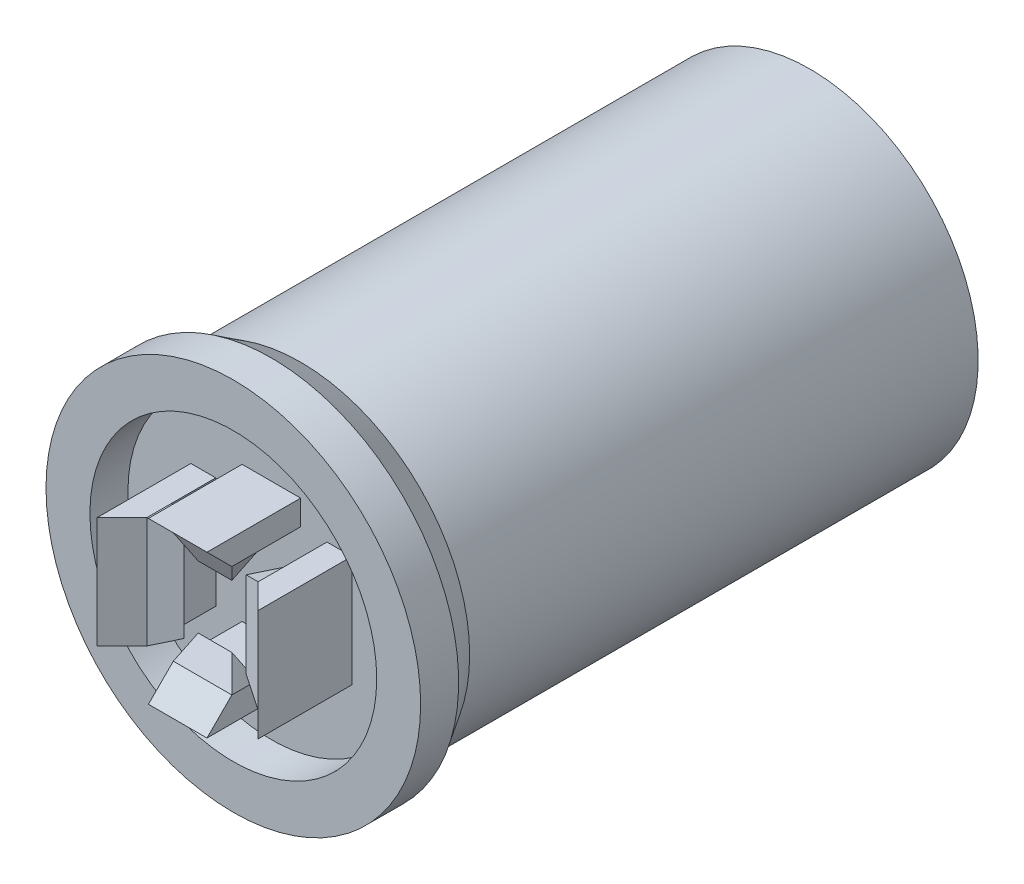
SolidWorks part; units mm, degrees
ref_plane "Front Plane" through (0, 0, 0) normal (0, 0, 1) x (1, 0, 0)
ref_plane "Top Plane" through (0, 0, 0) normal (0, 1, 0) x (1, 0, 0)
ref_plane "Right Plane" through (0, 0, 0) normal (1, 0, 0) x (0, 0, -1)
sketch "Sketch1" plane through (0, 0, 0) normal (0, 0, 1) x (1, 0, 0)
  circle A0 centre (0, 0) radius 6.4
  dimension "D1" = 12.8
extrude "Boss-Extrude1" add sketch "Sketch1" along normal blind 1.3
sketch "Sketch3" plane through (0, 0, 0) normal (0, 0, -1) x (-1, 0, 0)
  circle A0 centre (0, 0) radius 5.75
  dimension "D1" = 11.5
extrude "Boss-Extrude2" add sketch "Sketch3" along normal blind 18.4
sketch "Sketch2" plane through (0, 0, 1.3) normal (0, 0, 1) x (1, 0, 0)
  circle A0 centre (0, 0) radius 4.9
  dimension "D1" = 9.8
extrude "Cut-Extrude1" cut sketch "Sketch2" against normal blind 16.8
ref_plane "Plane1" through (0, 0, 3.2) normal (0, 0, 1) x (1, 0, 0)
sketch "Sketch4" plane through (0, 0, 3.2) normal (0, 0, 1) x (1, 0, 0)
  line L1 (-1, 2.75) -> (1, 2.75)
  line L2 (-1, 2.75) -> (-1, 1.9)
  line L3 (-1, 1.9) -> (1, 1.9)
  line L4 (1, 2.75) -> (1, 1.9)
  line L5 (-1, -1.9) -> (1, -1.9)
  line L6 (-1, -1.9) -> (-1, -2.75)
  line L7 (-1, -2.75) -> (1, -2.75)
  line L8 (1, -1.9) -> (1, -2.75)
  line L9 (1.9, 1.9) -> (2.75, 1.9)
  line L10 (1.9, 1.9) -> (1.9, -1.9)
  line L11 (1.9, -1.9) -> (2.75, -1.9)
  line L12 (2.75, 1.9) -> (2.75, -1.9)
  line L13 (-2.75, 1.9) -> (-1.9, 1.9)
  line L14 (-2.75, 1.9) -> (-2.75, -1.9)
  line L15 (-2.75, -1.9) -> (-1.9, -1.9)
  line L16 (-1.9, 1.9) -> (-1.9, -1.9)
  point P17 (-1.9, 0)
  point P18 (1.9, 0)
  point P19 (0, -2.75)
  point P20 (0, 2.75)
  dimension "D1" = 5.5
  dimension "D2" = 5.5
  dimension "D3" = 2
  dimension "D4" = 3.8
  dimension "D5" = 2.75
  dimension "D6" = 0.85
  dimension "D7" = 0.85
  dimension "D8" = 0.85
  dimension "D9" = 0.85
  dimension "D10" = 2.75
extrude "Boss-Extrude3" add sketch "Sketch4" against normal up to surface (18.7 mm away) up to face at (4.9, 0, -15.5)
chamfer "Chamfer1" distance 0.85 4 edges at (1.9, 0, 3.2) (-1.9, 0, 3.2) (0, -1.9, 3.2) (0, 1.9, 3.2)
sketch "Sketch5" plane through (1.9, 0, 0) normal (-1, 0, 0) x (0, 0, 1)
  line L0 (-15.5, 1.9) -> (2.35, 1.9) construction
  line L1 (2.35, -1.9) -> (1.5, -1.9)
  line L2 (2.35, -1.9) -> (2.35, 1.9)
  line L3 (2.35, 1.9) -> (1.5, 1.9)
  line L4 (1.5, -1.9) -> (1.5, 1.9)
  dimension "D1" = 0.85
extrude "Boss-Extrude4" add sketch "Sketch5" along normal blind 0.85 draft 27
mirror "Mirror1" about plane through (0, 0, 0) normal (1, 0, 0) of "Boss-Extrude4"
sketch "Sketch6" plane through (0, 1.9, 0) normal (0, -1, 0) x (1, 0, 0)
  line L0 (-1, -15.5) -> (-1, 2.35) construction
  line L1 (-1, 2.35) -> (1, 2.35)
  line L2 (-1, 2.35) -> (-1, 1.5)
  line L3 (-1, 1.5) -> (1, 1.5)
  line L4 (1, 2.35) -> (1, 1.5)
  line L5 (1, -15.5) -> (1, 2.35) construction
  line L6 (1, 2.35) -> (-1, 2.35) construction
  dimension "D1" = 0.85
extrude "Boss-Extrude5" add sketch "Sketch6" along normal blind 0.85 draft 27
mirror "Mirror2" about plane through (0, 0, 0) normal (0, 1, 0) of "Boss-Extrude5"
sketch "Sketch7" plane through (0, 0, 0) normal (0, 0, -1) x (-1, 0, 0)
  circle A0 centre (0, 0) radius 6.4 construction
  circle A1 centre (0, 0) radius 6.4
extrude "Boss-Extrude6" add sketch "Sketch7" along normal blind 1 draft 32
